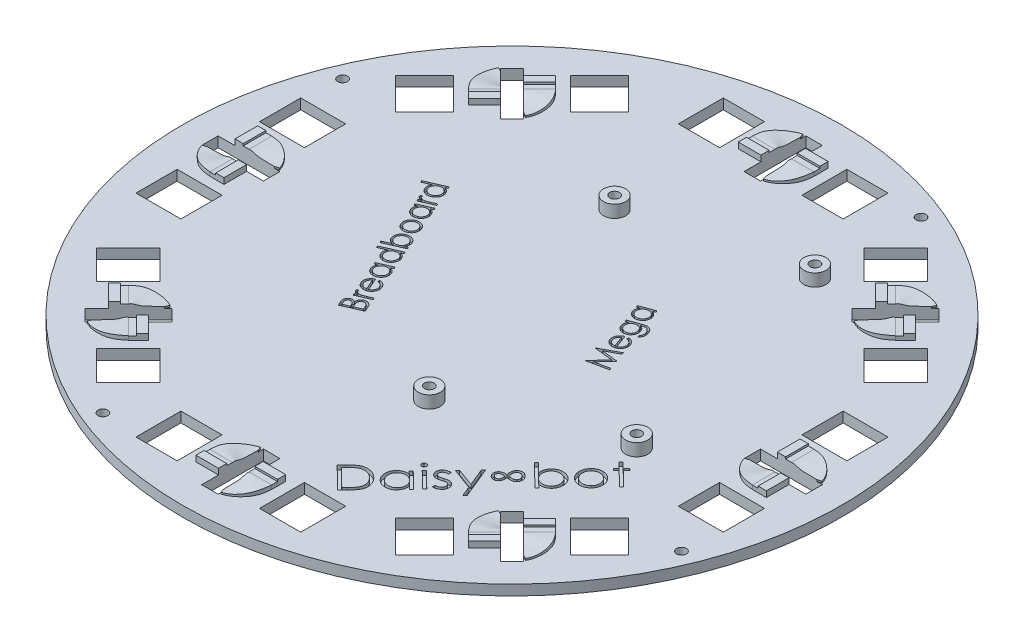
SolidWorks part; units mm, degrees
ref_plane "Front" through (0, 0, 0) normal (0, 0, 1) x (1, 0, 0)
ref_plane "Top" through (0, 0, 0) normal (0, 1, 0) x (1, 0, 0)
ref_plane "Right" through (0, 0, 0) normal (1, 0, 0) x (0, 0, -1)
sketch "Sketch1" plane through (0, 0, 0) normal (0, 1, 0) x (1, 0, 0)
  circle A0 centre (0, 0) radius 101.6
  dimension "D1" = 203.2
extrude "Boss-Extrude1" add sketch "Sketch1" along normal blind 3.175 contours A0
sketch "Sketch2" plane through (0, 3.175, 0) normal (0, 1, 0) x (1, 0, 0)
  line L1 (-2.54, -93.1333) -> (2.54, -93.1333)
  line L2 (-2.54, -93.1333) -> (-2.54, -74.0833)
  line L3 (-2.54, -74.0833) -> (2.54, -74.0833)
  line L4 (2.54, -93.1333) -> (2.54, -74.0833)
  point P4 (0, -74.0833)
  dimension "D1" = 5.08
  dimension "D2" = 19.05
  dimension "D3" = 93.1333
extrude "Cut-Extrude1" cut sketch "Sketch2" against normal up to next and the other way through all contours L1 L4 L3 L2
sketch "Sketch4" plane through (0, 3.175, 0) normal (0, 1, 0) x (1, 0, 0)
  line L0 (0, -83.6083) -> (-2.9434, -74.5495) construction
  line L1 (-2.9434, -74.5495) -> (0, -83.6083) construction
  line L2 (0, -83.6083) -> (-5.5987, -75.9024) construction
  line L3 (0, -83.6083) -> (-7.7059, -78.0097) construction
  line L4 (0, -83.6083) -> (-9.0588, -80.6649) construction
  line L5 (0, -83.6083) -> (-9.525, -83.6083) construction
  line L9 (2.54, -74.0833) -> (-2.54, -74.0833) construction
  line L10 (2.54, -74.0833) -> (2.54, -93.1333) construction
  line L11 (-2.54, -74.0833) -> (-2.54, -93.1333) construction
  line L12 (2.54, -93.1333) -> (-2.54, -93.1333) construction
  circle A0 centre (0, -83.6083) radius 9.525 construction
  point P16 (0, -74.0833)
  point P19 (2.54, -83.6083)
  dimension "D1" = 18
  dimension "D2" = 18
  dimension "D3" = 18
  dimension "D4" = 18
  dimension "D5" = 18
ref_plane "Plane1" through (-24.5719, 0, 7.9839) normal (0.9511, 0, -0.309) x (-0.309, 0, -0.9511)
ref_plane "Plane2" through (-39.7581, 0, 28.886) normal (0.809, 0, -0.5878) x (-0.5878, 0, -0.809)
ref_plane "Plane3" through (-39.7581, 0, 54.7224) normal (0.5878, 0, -0.809) x (-0.809, 0, -0.5878)
ref_plane "Plane4" through (-24.5719, 0, 75.6244) normal (0.309, 0, -0.9511) x (-0.9511, 0, -0.309)
ref_plane "Plane5" through (0, 0, 83.6083) normal (0, 0, -1) x (-1, 0, 0)
sketch "Sketch5" plane through (-24.5719, 0, 7.9839) normal (0.9511, 0, -0.309) x (-0.309, 0, -0.9511)
  line L0 (-69.6725, 3.175) -> (-87.7902, 3.175) construction
  line L1 (-71.2966, 3.175) -> (-69.9913, 3.175)
  line L2 (-71.2966, 3.175) -> (-71.2966, 3.683)
  line L3 (-71.2966, 3.683) -> (-69.9913, 3.683)
  line L4 (-69.9913, 3.175) -> (-69.9913, 3.683)
  dimension "D2" = 0.508
sketch "Sketch6" plane through (-39.7581, 0, 28.886) normal (0.809, 0, -0.5878) x (-0.5878, 0, -0.809)
  line L0 (-58.4417, 3.175) -> (-73.8535, 3.175) construction
  line L1 (-63.3193, 3.175) -> (-58.1156, 3.175)
  line L2 (-63.3193, 3.175) -> (-63.3193, 3.775)
  line L3 (-63.3193, 3.775) -> (-58.1156, 3.775)
  line L4 (-58.1156, 3.175) -> (-58.1156, 3.775)
  dimension "D2" = 0.6
sketch "Sketch7" plane through (-39.7581, 0, 54.7224) normal (0.5878, 0, -0.809) x (-0.809, 0, -0.5878)
  line L0 (-41.4902, 3.175) -> (-52.6875, 3.175) construction
  line L1 (-46.0041, 3.175) -> (-39.6187, 3.175)
  line L2 (-46.0041, 3.175) -> (-46.0041, 4.075)
  line L3 (-46.0041, 4.075) -> (-39.6187, 4.075)
  line L4 (-39.6187, 3.175) -> (-39.6187, 4.075)
  dimension "D2" = 0.9
sketch "Sketch10" plane through (-24.5719, 0, 75.6244) normal (0.309, 0, -0.9511) x (-0.9511, 0, -0.309)
  line L0 (-25.8364, 3.175) -> (-16.7776, 3.175) construction
  line L1 (-23.1657, 3.175) -> (-16.3114, 3.175)
  line L2 (-23.1657, 3.175) -> (-23.1657, 4.375)
  line L3 (-23.1657, 4.375) -> (-16.3114, 4.375)
  line L4 (-16.3114, 3.175) -> (-16.3114, 4.375)
  dimension "D3" = 1.2
sketch "Sketch11" plane through (0, 0, 83.6083) normal (0, 0, -1) x (-1, 0, 0)
  line L0 (0, 3.175) -> (9.525, 3.175) construction
  line L1 (2.54, 3.175) -> (9.525, 3.175)
  line L2 (2.54, 3.175) -> (2.54, 4.375)
  line L3 (2.54, 4.375) -> (9.525, 4.375)
  line L4 (9.525, 3.175) -> (9.525, 4.375)
  dimension "D3" = 1.2
loft "Loft1" add profiles "Sketch5", "Sketch6", "Sketch7", "Sketch10", "Sketch11" connector at (-2.54, 3.683, 75.791) connector at (-2.54, 3.775, 80.1123) connector at (-2.54, 4.075, 81.7629) connector at (-2.54, 4.375, 82.783) connector at (-2.54, 4.375, 83.6083)
sketch "Sketch13" plane through (-104.9799, 0, 83.6083) normal (0, 0, -1) x (-1, 0, 0)
  line L6 (-95.4549, 3.175) -> (-102.4399, 3.175)
  line L7 (-95.4549, 3.175) -> (-95.4549, 4.375)
  line L8 (-95.4549, 4.375) -> (-102.4399, 4.375)
  line L9 (-102.4399, 3.175) -> (-102.4399, 4.375)
extrude "Boss-Extrude4" add sketch "Sketch13" against normal blind 1.7907
sketch "Sketch25" plane through (0, 0, 85.399) normal (0, 0, 1) x (1, 0, 0)
  line L0 (-9.525, 4.375) -> (-2.54, 4.375) construction
  line L1 (-9.525, 3.175) -> (-2.54, 3.175)
  line L2 (-9.525, 3.175) -> (-9.525, 4.975)
  line L3 (-9.525, 4.975) -> (-2.54, 4.975)
  line L4 (-2.54, 3.175) -> (-2.54, 4.975)
  dimension "D1" = 0.6
extrude "Boss-Extrude5" add sketch "Sketch25" along normal blind 2.54
sketch "Sketch14" plane through (-2.54, 0, 0) normal (1, 0, 0) x (0, 0, -1)
  line L0 (-83.6083, 3.175) -> (-83.6083, 0) construction
  line L1 (-74.0833, 0) -> (-93.1333, 0) construction
ref_plane "Plane6" through (0, 0, 0) normal (1, 0, 0) x (0, 0, -1)
sketch "Sketch15" plane through (0, 0, 0) normal (1, 0, 0) x (0, 0, -1)
  line L0 (-83.6083, 0) -> (-83.6083, 3.175) construction
pattern_circular "CirPattern1" count 2 over 360 about axis through (0, 0, 83.6083) along (0, 1, 0) of "Loft1", "Boss-Extrude5", "Boss-Extrude4" reverse direction yes
ref_axis "Axis1" through (0, 50, 0) along (0, -1, 0)
pattern_circular "CirPattern5" count 8 over 360 about axis through (0, 50, 0) along (0, -1, 0) of "CirPattern1", "Cut-Extrude1"
sketch "Sketch18" plane through (0, 3.175, 0) normal (0, 1, 0) x (1, 0, 0)
  line L0 (-12.3739, 44.0137) -> (36.5149, 57.7582) construction
  line L1 (-12.3739, 44.0137) -> (9.9679, -35.4555) construction
  line L2 (36.5149, 57.7582) -> (36.8586, 56.5356) construction
  line L3 (54.6967, -16.2402) -> (8.2378, -29.3015) construction
  line L4 (0, -101.6) -> (0, 101.6) construction
  line L5 (0, -1.7463) -> (0, 1.7463) construction
  line L6 (-101.6, 0) -> (101.6, 0) construction
  line L7 (36.8586, 56.5356) -> (54.6967, -16.2402) construction
  circle A0 centre (-12.3739, 44.0137) radius 3.405
  circle A1 centre (9.9679, -35.4555) radius 3.405
  circle A2 centre (54.6967, -16.2402) radius 3.405
  circle A3 centre (36.8586, 56.5356) radius 3.405
  circle A4 centre (9.9679, -35.4555) radius 1.5
  circle A5 centre (-12.3739, 44.0137) radius 1.5
  circle A6 centre (36.8586, 56.5356) radius 1.5
  circle A7 centre (54.6967, -16.2402) radius 1.5
  circle A8 centre (0, 0) radius 101.6 construction
  dimension "D7" = 1.905
  dimension "D8" = 3
  dimension "D9" = 1.27
  dimension "D1" = 82.55
  dimension "D2" = 74.93
  dimension "D3" = 50.8
  dimension "D4" = 15.703
  dimension "D5" = 36.83
  dimension "D10" = 48.26
sketch "Sketch19" plane through (0, 3.175, 0) normal (0, 1, 0) x (1, 0, 0)
  line L0 (-36.9366, -89.1729) -> (0, 0) construction
  line L1 (0, -101.6) -> (0, 101.6) construction
  circle A1 centre (-36.9366, -89.1729) radius 1.5
  circle A4 centre (0, 0) radius 101.6 construction
  dimension "D4" = 3
  dimension "D6" = 96.52
  dimension "D5" = 22.5
extrude "Cut-Extrude2" cut sketch "Sketch19" against normal through all
pattern_circular "CirPattern7" count 4 over 360 about axis through (0, 50, 0) along (0, -1, 0) of "Cut-Extrude2"
extrude "Boss-Extrude3" add sketch "Sketch18" along normal blind 3.81
sketch "Sketch23" plane through (0, 3.175, 0) normal (0, 1, 0) x (1, 0, 0)
  line L9 (-2.54, -87.939) -> (-2.54, -93.1333) construction
  line L10 (-25.4, -76.6805) -> (-12.7, -76.6805)
  line L11 (-25.4, -76.6805) -> (-25.4, -90.5362)
  line L16 (-25.4, -90.5362) -> (-12.7, -90.5362)
  line L17 (-12.7, -76.6805) -> (-12.7, -90.5362)
  line L19 (2.54, -74.0833) -> (2.54, -79.2776) construction
  line L20 (0, -50) -> (0, 50) construction
  line L21 (12.7, -76.6805) -> (12.7, -90.5362)
  line L22 (25.4, -90.5362) -> (12.7, -90.5362)
  line L23 (25.4, -76.6805) -> (25.4, -90.5362)
  line L24 (25.4, -76.6805) -> (12.7, -76.6805)
  point P8 (-2.54, -90.5362)
  point P9 (2.54, -76.6805)
  dimension "D1" = 12.7
  dimension "D2" = 10.16
extrude "Cut-Extrude6" cut sketch "Sketch23" against normal through all
pattern_circular "CirPattern8" count 8 over 360 about axis through (0, 50, 0) along (0, -1, 0) of "Cut-Extrude6"
sketch "Sketch17" plane through (0, 3.175, 0) normal (0, 1, 0) x (1, 0, 0)
  line L0 (19.0413, -74.398) -> (63.1398, -28.708) construction
  dimension "D2" = 74.398
  dimension "D1" = 63.5
  dimension "D3" = 69.3598
  dimension "D4" = 76.796
sketch "Sketch16" plane through (0, 3.175, 0) normal (0, 1, 0) x (1, 0, 0)
  line L0 (19.0413, -74.398) -> (63.1398, -28.708) construction
  line L1 (25.4, -76.6805) -> (12.7, -76.6805) construction
  text T0 "Daisy∞bot\r\n" font "Century Gothic" height in points 36
extrude "Cut-Extrude4" cut sketch "Sketch16" against normal blind 1.27
sketch "Sketch22" plane through (0, 3.175, 0) normal (0, 1, 0) x (1, 0, 0)
  line L0 (-44.1287, 25.1735) -> (-20.5694, -28.6741) construction
  text T0 "Breadboard"
extrude "Cut-Extrude5" cut sketch "Sketch22" against normal blind 1.27
sketch "Sketch24" plane through (0, 3.175, 0) normal (0, 1, 0) x (1, 0, 0)
  line L0 (29.8571, 0) -> (21.0896, 23.8389) construction
  text T0 "Mega"
  dimension "D1" = 28.022
  dimension "D2" = 25.4
  dimension "D3" = 29.8571
extrude "Cut-Extrude7" cut sketch "Sketch24" against normal blind 1.27
